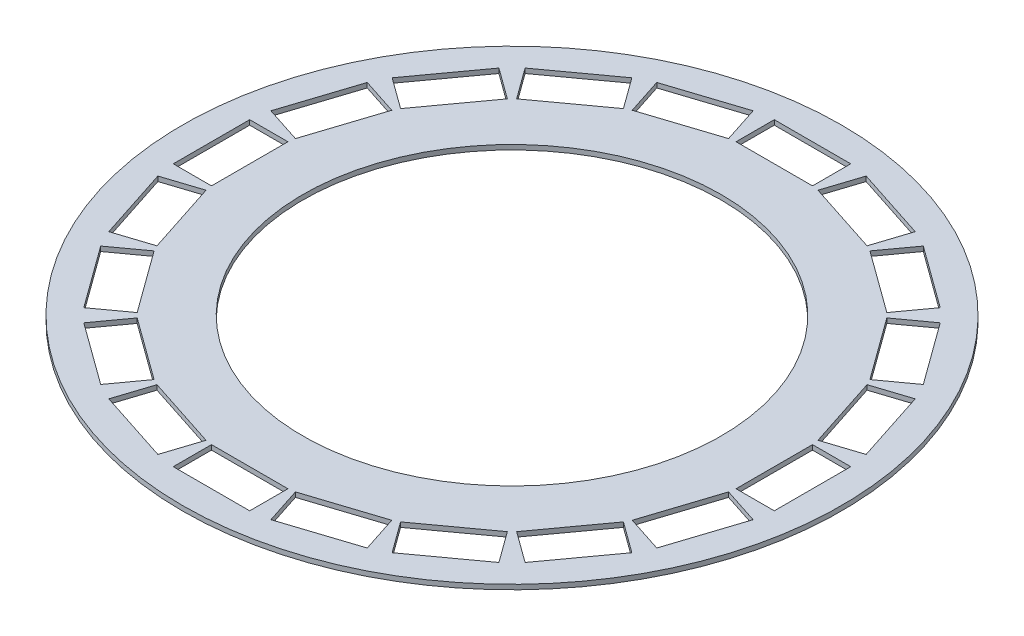
SolidWorks part; units mm, degrees
material "Hexcel AS4C (3000 Filaments)"
ref_plane "Front Plane" through (0, 0, 0) normal (0, 0, 1) x (1, 0, 0)
ref_plane "Top Plane" through (0, 0, 0) normal (0, 1, 0) x (1, 0, 0)
ref_plane "Right Plane" through (0, 0, 0) normal (1, 0, 0) x (0, 0, -1)
sketch "Sketch1" plane through (0, 0, 0) normal (0, 0, 1) x (1, 0, 0)
  line L0 (-69.5, 7.3725) -> (-69.5, 5.785) construction
  line L1 (-69.5, 7.3725) -> (-109.5, 7.3725) construction
  line L2 (-109.5, 5.785) -> (-69.5, 5.785) construction
  line L3 (-109.5, 7.3725) -> (-109.5, 5.785) construction
  line L4 (-69.5, 7.3725) -> (-69.5, 5.785)
  line L5 (-69.5, 7.3725) -> (-109.5, 7.3725)
  line L6 (-109.5, 5.785) -> (-69.5, 5.785)
  line L7 (-109.5, 7.3725) -> (-109.5, 5.785)
  line L8 (0, -200069.0475) -> (0, 200086.9028) construction
  line L9 (0, -200069.0475) -> (0, 200086.9028) construction
revolve "Revolve1" add sketch "Sketch1" angle 360 about L9
sketch "Sketch2" plane through (0, 7.3725, 0) normal (0, 1, 0) x (1, 0, 0)
  line L0 (0, 93.5) -> (0, 0) construction
  line L1 (-12.7, 99.85) -> (12.7, 99.85)
  line L2 (-12.7, 99.85) -> (-12.7, 87.15)
  line L3 (-12.7, 87.15) -> (12.7, 87.15)
  line L4 (12.7, 99.85) -> (12.7, 87.15)
  line L5 (-12.7, 99.85) -> (12.7, 87.15) construction
  line L6 (-12.7, 87.15) -> (12.7, 99.85) construction
  line L7 (0, 100) -> (0, 87) construction
  circle A0 centre (0, 0) radius 87 construction
  circle A1 centre (0, 0) radius 100 construction
  circle A2 centre (0, 0) radius 87 construction
  circle A3 centre (0, 0) radius 100 construction
  point P0 (0, 93.5)
  dimension "D1" = 12.7
  dimension "D2" = 25.4
extrude "Cut-Extrude1" cut sketch "Sketch2" against normal through all
pattern_circular "CirPattern1" count 20 over 360 about axis through (0, -200069.0475, 0) along (0, -1, 0) of "Cut-Extrude1"
